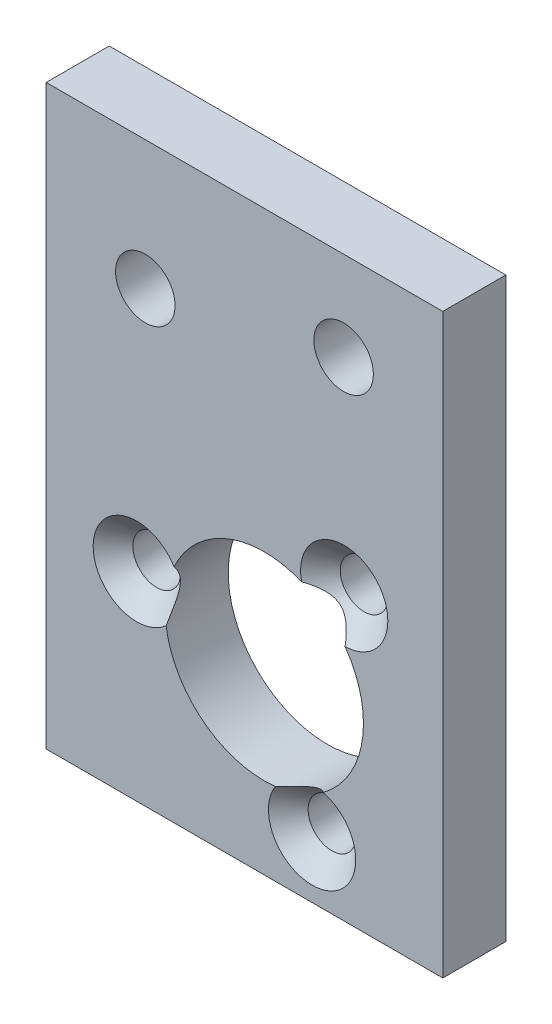
SolidWorks part; units mm, degrees
ref_plane "Front Plane" through (0, 0, 0) normal (0, 0, 1) x (1, 0, 0)
ref_plane "Top Plane" through (0, 0, 0) normal (0, 1, 0) x (1, 0, 0)
ref_plane "Right Plane" through (0, 0, 0) normal (1, 0, 0) x (0, 0, -1)
sketch "Sketch1" plane through (0, 0, 0) normal (0, 0, 1) x (1, 0, 0)
  line L1 (0, 0) -> (20, 0)
  line L2 (0, 0) -> (0, 29.11)
  line L3 (0, 29.11) -> (20, 29.11)
  line L4 (20, 0) -> (20, 29.11)
  circle A0 centre (5, 22.61) radius 1.5
  circle A1 centre (15, 24.61) radius 1.5
  arc A2 (15.0728, 12.0104) -> (12.8801, 13.743) centre (15.03, 14.21) ccw
  arc A3 (6.4499, 11.1828) -> (6.049, 8.4114) centre (4.57, 10.04) ccw
  arc A4 (11.5537, 4.1408) -> (13.9699, 5.0876) centre (13.41, 2.96) ccw
  circle A7 centre (15.03, 14.21) radius 1.2
  circle A8 centre (4.57, 10.04) radius 1.2
  circle A9 centre (13.41, 2.96) radius 1.2
  circle A10 centre (11, 9.11) radius 5
extrude "Boss-Extrude2" add sketch "Sketch1" against normal blind 3.18 contours A0 | A1 | L2 L1 L4 L3 | A7 | A10 | A8 | A9 region at (5, 22.61, 0) region at (15, 24.61, 0)
hole_wizard "CSK for M2 Flat Head Machine Screw1" positions "Sketch10" profile "Sketch11" countersink size "M2" standard "ANSI Metric"
sketch "Sketch10" plane through (0, 0, 0) normal (0, 0, 1) x (1, 0, 0)
  point P0 (4.57, 10.04)
  point P3 (15.03, 14.21)
  point P6 (13.41, 2.96)
sketch "Sketch11" plane through (4.57, 10.04, 0) normal (1, 0, 0) x (0, -1, 0)
  line L0 (0, 0) -> (0, 4.23)
  line L1 (0, 4.23) -> (1.2, 3.509)
  line L2 (1.2, 3.509) -> (1.2, 1)
  line L3 (1.2, 1) -> (2.2, 0)
  line L5 (2.2, 0) -> (0, 0)
  line L6 (-1.2, 1) -> (-2.2, 0) construction
  line L10 (0, 4.23) -> (-1.2, 3.509) construction
  line L11 (0, -6.35) -> (0, 107.95) construction
  dimension "Hole Dia." = 2.4
  dimension "Hole Depth" = 4.23
  dimension "Near C'Sink Dia." = 4.4
  dimension "Near C'Sink Angle" = 90
  dimension "Drill Angle" = 118
